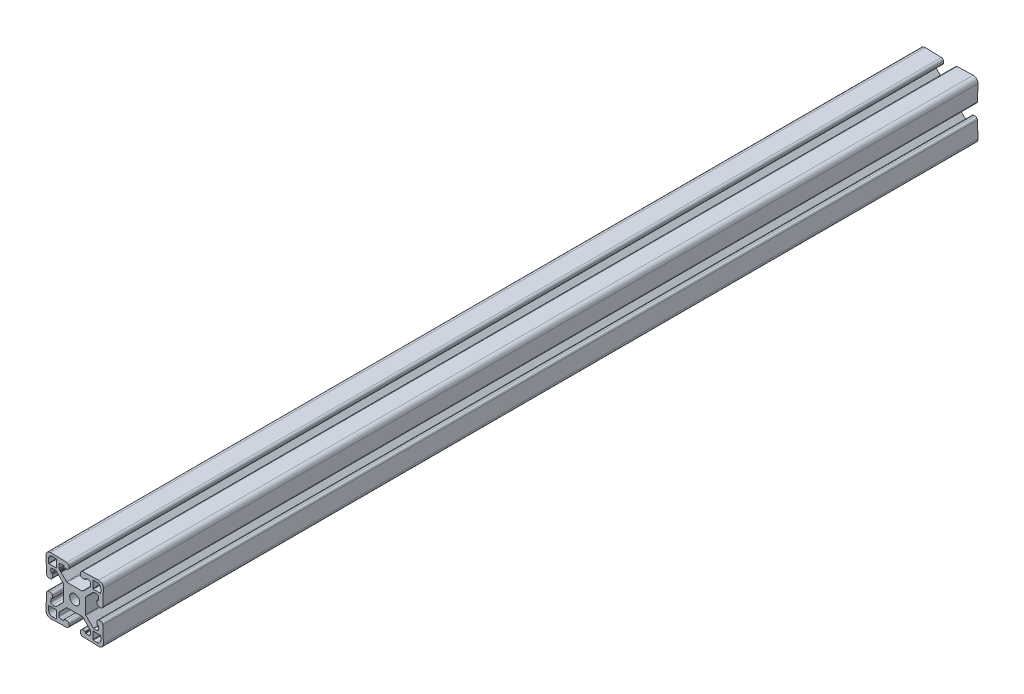
SolidWorks part; units mm, degrees
ref_plane "Front Plane" through (0, 0, 0) normal (0, 0, 1) x (1, 0, 0)
ref_plane "Top Plane" through (0, 0, 0) normal (0, 1, 0) x (1, 0, 0)
ref_plane "Right Plane" through (0, 0, 0) normal (1, 0, 0) x (0, 0, -1)
sketch "Sketch1" plane through (0, 0, 0) normal (0, 0, 1) x (1, 0, 0)
  line L0 (0, 0) -> (0, 20) construction
  line L1 (0, 0) -> (20, 0) construction
  line L2 (0, 0) -> (-20, 20) construction
  line L3 (-16.7142, 19.9981) -> (-5.5358, 19.6077)
  line L4 (-20, 20) -> (0, 20) construction
  line L5 (-4.064, 18.0836) -> (-4.064, 17.069)
  line L6 (-5.6422, 15.5449) -> (-7.1936, 15.5991)
  line L7 (-7.5, 15.9164) -> (-7.5, 16.3198)
  line L8 (-7.8064, 16.6371) -> (-9.6857, 16.7028)
  line L9 (-11, 15.4335) -> (-11, 13.2868)
  line L10 (0, 7.681) -> (-5.2101, 7.681)
  line L11 (-5.7489, 7.9042) -> (-10.907, 13.0623)
  line L12 (-7.9042, 5.7489) -> (-13.0623, 10.907)
  line L13 (-7.681, 0) -> (-7.681, 5.2101)
  line L14 (-15.4335, 11) -> (-13.2868, 11)
  line L15 (-16.6371, 7.8064) -> (-16.7028, 9.6857)
  line L16 (-15.9164, 7.5) -> (-16.3198, 7.5)
  line L17 (-15.5449, 5.6422) -> (-15.5991, 7.1936)
  line L18 (-18.0836, 4.064) -> (-17.069, 4.064)
  line L19 (-19.9981, 16.7142) -> (-19.6077, 5.5358)
  line L20 (-18.2207, 15.3309) -> (-18.1275, 12.661)
  line L21 (-15.3309, 18.2207) -> (-12.661, 18.1275)
  line L22 (-18.1275, 12.661) -> (-12.661, 12.661)
  line L23 (-12.661, 18.1275) -> (-12.661, 12.661)
  line L24 (0, 0) -> (-20, 0) construction
  line L25 (-20, 0) -> (0, 0) construction
  line L26 (0, 0) -> (0, -20) construction
  line L27 (-20, -20) -> (-20, 20) construction
  line L28 (0, 20) -> (20, 20) construction
  line L29 (0, -1000) -> (0, 49000)
  line L30 (-20, -20) -> (20, -20) construction
  arc A0 (-19.9981, 16.7142) -> (-16.7142, 19.9981) centre (-16.825, 16.825) cw
  arc A1 (-7.1936, 15.5991) -> (-7.5, 15.9164) centre (-7.1825, 15.9164) cw
  arc A2 (-7.5, 16.3198) -> (-7.8064, 16.6371) centre (-7.8175, 16.3198) ccw
  arc A3 (-9.6857, 16.7028) -> (-11, 15.4335) centre (-9.73, 15.4335) ccw
  arc A4 (-4.064, 17.069) -> (-5.6422, 15.5449) centre (-5.589, 17.069) cw
  arc A5 (-5.5358, 19.6077) -> (-4.064, 18.0836) centre (-5.589, 18.0836) cw
  arc A6 (-5.2101, 7.681) -> (-5.7489, 7.9042) centre (-5.2101, 8.443) cw
  arc A7 (-7.9042, 5.7489) -> (-7.681, 5.2101) centre (-8.443, 5.2101) cw
  arc A8 (-11, 13.2868) -> (-10.907, 13.0623) centre (-10.6825, 13.2868) ccw
  arc A9 (-18.0836, 4.064) -> (-19.6077, 5.5358) centre (-18.0836, 5.589) cw
  arc A10 (-15.5449, 5.6422) -> (-17.069, 4.064) centre (-17.069, 5.589) cw
  arc A11 (-15.9164, 7.5) -> (-15.5991, 7.1936) centre (-15.9164, 7.1825) cw
  arc A12 (-16.6371, 7.8064) -> (-16.3198, 7.5) centre (-16.3198, 7.8175) ccw
  arc A13 (-15.4335, 11) -> (-16.7028, 9.6857) centre (-15.4335, 9.73) ccw
  arc A14 (-13.0623, 10.907) -> (-13.2868, 11) centre (-13.2868, 10.6825) ccw
  arc A15 (-15.3309, 18.2207) -> (-18.2207, 15.3309) centre (-15.4284, 15.4284) ccw
  circle A16 centre (0, 0) radius 3.5
  point P26 (-7.5, 15.6098)
  point P29 (-7.5, 16.6264)
  point P32 (-11, 16.7487)
  point P35 (-4.064, 15.4898)
  point P38 (-4.064, 19.5563)
  point P42 (-5.5257, 7.681)
  point P45 (-7.681, 5.5257)
  point P48 (-11, 13.1553)
  point P51 (-19.5563, 4.064)
  point P54 (-15.4898, 4.064)
  point P57 (-15.6098, 7.5)
  point P60 (-16.6264, 7.5)
  point P63 (-16.7487, 11)
  point P66 (-13.1553, 11)
  point P80 (-20, 0)
  point P85 (0, -20)
  point P88 (0, -20)
  dimension "D11" = 3.175
  dimension "D14" = 1.27
  dimension "D16" = 1.525
  dimension "D15" = 0.762
  dimension "D21" = 2.794
  dimension "D4" = 0.3175
  dimension "Center Hole Diameter" = 7
  dimension "D1" = 45
  dimension "D2" = 2
  dimension "Rail Width" = 40
  dimension "T-Slot Width" = 8.128
  dimension "D6" = 3.048
  dimension "D10" = 3.048
  dimension "D13" = 1.728
  dimension "D8" = 22
  dimension "D18" = 1.661
  dimension "D19" = 7.339
  dimension "D20" = 7.339
  dimension "T-Slot Depth" = 12.319
  dimension "D9" = 4.064
  dimension "Rail Height1" = 40
  dimension "Rail Height" = 40
  dimension "D23" = 15.362
  dimension "D3" = 20
  dimension "D7" = 3.5
sketch "Sketch2" plane through (0, 0, 0) normal (1, 0, 0) x (0, 0, -1)
  line L0 (-304.8, 0) -> (304.8, 0)
  line L1 (-304.8, -20) -> (-304.8, 20) construction
  line L2 (0, 0) -> (0, 20) construction
  line L3 (0, 0) -> (0, 20) construction
  line L4 (304.8, -20) -> (304.8, 20) construction
  point P0 (-244.8, 0)
  point P3 (0, 0)
  point P7 (244.8, 0)
  point P11 (-304.8, 0)
  point P14 (304.8, 0)
  dimension "D1" = 60
  dimension "Length" = 609.6
sketch "Sketch3" plane through (0, 0, 0) normal (0, 0, 1) x (1, 0, 0)
  line L0 (-7.681, 0) -> (-7.681, 5.2101) construction
  line L1 (-7.9042, 5.7489) -> (-13.0623, 10.907) construction
  line L2 (-15.4335, 11) -> (-13.2868, 11) construction
  line L3 (-16.6371, 7.8064) -> (-16.7028, 9.6857) construction
  line L4 (-18.2207, 15.3309) -> (-18.1275, 12.661)
  line L5 (-18.1275, 12.661) -> (-12.661, 12.661)
  line L6 (-12.661, 12.661) -> (-12.661, 18.1275)
  line L7 (-12.661, 18.1275) -> (-15.3309, 18.2207)
  line L8 (-18.2207, 15.3309) -> (-18.136, 12.9061)
  line L9 (-17.8822, 12.661) -> (-12.915, 12.661)
  line L10 (-12.661, 12.915) -> (-12.661, 17.8822)
  line L11 (-12.9061, 18.136) -> (-15.3309, 18.2207)
  line L12 (-15.9164, 7.5) -> (-16.3198, 7.5) construction
  line L13 (-15.5449, 5.6422) -> (-15.5991, 7.1936) construction
  line L14 (-18.0836, 4.064) -> (-17.069, 4.064) construction
  line L15 (-19.9981, 16.7142) -> (-19.6077, 5.5358) construction
  line L16 (-16.7142, 19.9981) -> (-5.5358, 19.6077) construction
  line L17 (-4.064, 18.0836) -> (-4.064, 17.069) construction
  line L18 (-5.6422, 15.5449) -> (-7.1936, 15.5991) construction
  line L19 (-7.5, 15.9164) -> (-7.5, 16.3198) construction
  line L20 (-7.8064, 16.6371) -> (-9.6857, 16.7028) construction
  line L21 (-11, 15.4335) -> (-11, 13.2868) construction
  line L22 (-5.7489, 7.9042) -> (-10.907, 13.0623) construction
  line L23 (0, 7.681) -> (-5.2101, 7.681) construction
  line L24 (-7.681, 0) -> (-7.681, 5.2101)
  line L25 (-7.9042, 5.7489) -> (-13.0623, 10.907)
  line L26 (-15.4335, 11) -> (-13.2868, 11)
  line L27 (-16.6371, 7.8064) -> (-16.7028, 9.6857)
  line L28 (-15.9164, 7.5) -> (-16.3198, 7.5)
  line L29 (-15.5449, 5.6422) -> (-15.5991, 7.1936)
  line L30 (-18.0836, 4.064) -> (-17.069, 4.064)
  line L31 (-19.9981, 16.7142) -> (-19.6077, 5.5358)
  line L32 (-16.7142, 19.9981) -> (-5.5358, 19.6077)
  line L33 (-4.064, 18.0836) -> (-4.064, 17.069)
  line L34 (-5.6422, 15.5449) -> (-7.1936, 15.5991)
  line L35 (-7.5, 15.9164) -> (-7.5, 16.3198)
  line L36 (-7.8064, 16.6371) -> (-9.6857, 16.7028)
  line L37 (-11, 15.4335) -> (-11, 13.2868)
  line L38 (-5.7489, 7.9042) -> (-10.907, 13.0623)
  line L39 (0, 7.681) -> (-5.2101, 7.681)
  line L40 (-7.681, 0) -> (-3.5, 0)
  line L41 (0, 3.5) -> (0, 7.681)
  arc A0 (-7.681, 5.2101) -> (-7.9042, 5.7489) centre (-8.443, 5.2101) ccw construction
  circle A1 centre (0, 0) radius 3.5
  arc A2 (0, 3.5) -> (-3.5, 0) centre (0, 0) ccw
  arc A3 (-15.3309, 18.2207) -> (-18.2207, 15.3309) centre (-15.4284, 15.4284) ccw
  arc A4 (-15.3309, 18.2207) -> (-18.2207, 15.3309) centre (-15.4284, 15.4284) ccw
  arc A5 (-13.0623, 10.907) -> (-13.2868, 11) centre (-13.2868, 10.6825) ccw construction
  arc A6 (-15.4335, 11) -> (-16.7028, 9.6857) centre (-15.4335, 9.73) ccw construction
  arc A7 (-16.6371, 7.8064) -> (-16.3198, 7.5) centre (-16.3198, 7.8175) ccw construction
  arc A8 (-15.5991, 7.1936) -> (-15.9164, 7.5) centre (-15.9164, 7.1825) ccw construction
  arc A9 (-17.069, 4.064) -> (-15.5449, 5.6422) centre (-17.069, 5.589) ccw construction
  arc A10 (-19.6077, 5.5358) -> (-18.0836, 4.064) centre (-18.0836, 5.589) ccw construction
  arc A11 (-16.7142, 19.9981) -> (-19.9981, 16.7142) centre (-16.825, 16.825) ccw construction
  arc A12 (-4.064, 18.0836) -> (-5.5358, 19.6077) centre (-5.589, 18.0836) ccw construction
  arc A13 (-5.6422, 15.5449) -> (-4.064, 17.069) centre (-5.589, 17.069) ccw construction
  arc A14 (-7.5, 15.9164) -> (-7.1936, 15.5991) centre (-7.1825, 15.9164) ccw construction
  arc A15 (-7.5, 16.3198) -> (-7.8064, 16.6371) centre (-7.8175, 16.3198) ccw construction
  arc A16 (-9.6857, 16.7028) -> (-11, 15.4335) centre (-9.73, 15.4335) ccw construction
  arc A17 (-11, 13.2868) -> (-10.907, 13.0623) centre (-10.6825, 13.2868) ccw construction
  arc A18 (-5.7489, 7.9042) -> (-5.2101, 7.681) centre (-5.2101, 8.443) ccw construction
  arc A19 (-7.681, 5.2101) -> (-7.9042, 5.7489) centre (-8.443, 5.2101) ccw
  arc A20 (-13.0623, 10.907) -> (-13.2868, 11) centre (-13.2868, 10.6825) ccw
  arc A21 (-15.4335, 11) -> (-16.7028, 9.6857) centre (-15.4335, 9.73) ccw
  arc A22 (-16.6371, 7.8064) -> (-16.3198, 7.5) centre (-16.3198, 7.8175) ccw
  arc A23 (-15.5991, 7.1936) -> (-15.9164, 7.5) centre (-15.9164, 7.1825) ccw
  arc A24 (-17.069, 4.064) -> (-15.5449, 5.6422) centre (-17.069, 5.589) ccw
  arc A25 (-19.6077, 5.5358) -> (-18.0836, 4.064) centre (-18.0836, 5.589) ccw
  arc A26 (-16.7142, 19.9981) -> (-19.9981, 16.7142) centre (-16.825, 16.825) ccw
  arc A27 (-4.064, 18.0836) -> (-5.5358, 19.6077) centre (-5.589, 18.0836) ccw
  arc A28 (-5.6422, 15.5449) -> (-4.064, 17.069) centre (-5.589, 17.069) ccw
  arc A29 (-7.5, 15.9164) -> (-7.1936, 15.5991) centre (-7.1825, 15.9164) ccw
  arc A30 (-7.5, 16.3198) -> (-7.8064, 16.6371) centre (-7.8175, 16.3198) ccw
  arc A31 (-9.6857, 16.7028) -> (-11, 15.4335) centre (-9.73, 15.4335) ccw
  arc A32 (-11, 13.2868) -> (-10.907, 13.0623) centre (-10.6825, 13.2868) ccw
  arc A33 (-5.7489, 7.9042) -> (-5.2101, 7.681) centre (-5.2101, 8.443) ccw
  arc A36 (-12.661, 17.8822) -> (-12.9061, 18.136) centre (-12.915, 17.8822) ccw
  arc A37 (-12.915, 12.661) -> (-12.661, 12.915) centre (-12.915, 12.915) ccw
  arc A38 (-18.136, 12.9061) -> (-17.8822, 12.661) centre (-17.8822, 12.915) ccw
  dimension "D3" = 0.254
  dimension "D1" = 0
  dimension "D2" = 0
extrude "Boss-Extrude1" add sketch "Sketch3" along normal mid plane 609.6
pattern_circular "CirPattern1" count 4 over 360 about axis through (0, 0, 304.8) along (0, 0, -1) of "Boss-Extrude1"
sketch "Sketch4" plane through (0, 0, 0) normal (0, 0, 1) x (1, 0, 0)
  line L1 (-10.5057, 12.661) -> (-9.5057, 12.661)
  line L8 (-5.7489, 7.9042) -> (-10.907, 13.0623) construction
  line L9 (-9.5057, 12.661) -> (-9.5057, 11.661)
  line L10 (-9.5057, 11.661) -> (-9.8391, 11.661)
  line L12 (-10.1724, 12.3277) -> (-9.8391, 11.9943)
  line L20 (-9.8391, 11.9943) -> (-9.8391, 12.3277) construction
  line L22 (-9.8391, 11.661) -> (-9.8391, 11.9943)
  line L23 (-9.8391, 12.3277) -> (-10.1724, 12.3277) construction
  line L25 (-10.1724, 12.3277) -> (-10.5057, 12.3277)
  line L26 (-10.5057, 12.3277) -> (-10.5057, 12.661)
  line L27 (-17.8822, 12.661) -> (-12.915, 12.661) construction
  dimension "D2" = 1
extrude "Cut-Extrude1" cut sketch "Sketch4" against normal through all both and the other way through all
ref_plane "Contact Plane 1" through (0, 20, 0) normal (0, 1, 0) x (1, 0, 0)
ref_plane "Contact Plane 2" through (20, 0, 0) normal (1, 0, 0) x (0, 0, -1)
ref_plane "Contact Plane 3" through (0, -20, 0) normal (0, -1, 0) x (-1, 0, 0)
ref_plane "Contact Plane 4" through (-20, 0, 0) normal (-1, 0, 0) x (0, 0, 1)
equation "\"D1@Sketch2\"=\"Rail Width@Sketch1\"*1.5"
equation "\"D1@Boss-Extrude1\"=\"Length@Sketch2\""
equation "\"ShaftDiameter\"= 12mm"
equation "\"PendulumDiameter\"=12mm"
equation "\"PendulumLength\"= 140mm"
equation "\"EncoderOuterDiameter\"=1.5"
equation "\"EncoderShaftDiameter\"= 6mm"
equation "\"EncoderShaftLength\"=15mm+.5in+3mm"
equation "\"PendulumHolderangle\"=60"
equation "\"PendulumholderBottomHeight\"= 75"
equation "\"PendulumholderBottomWidth\"= 75"
equation "\"PendulumholderHeight\"=25"
equation "\"BearingOutsideDiameter\"=21mm"
equation "\"PendulumHolderWidth\"= 100mm"
equation "\"ShaftHeightFromTSlot\"= 100mm"
equation "\"BearingThickness\"= 5mm"
equation "\"SlipRingOuterDiameter\"=56mm"
equation "\"SlipringBigThickness\"=25mm"
equation "\"SlipringSmallThickness\"=8.5mm"
equation "\"Tol\"=2mm"
equation "\"ScrewHole\"= 5mm"
equation "\"Tframwidth\"= 40mm"
equation "\"TFrameheight\"= 12in"
equation "\"Tframetotalwidth\"= 2ft"
equation "\"Length@Sketch2\"=\"Tframetotalwidth\""
